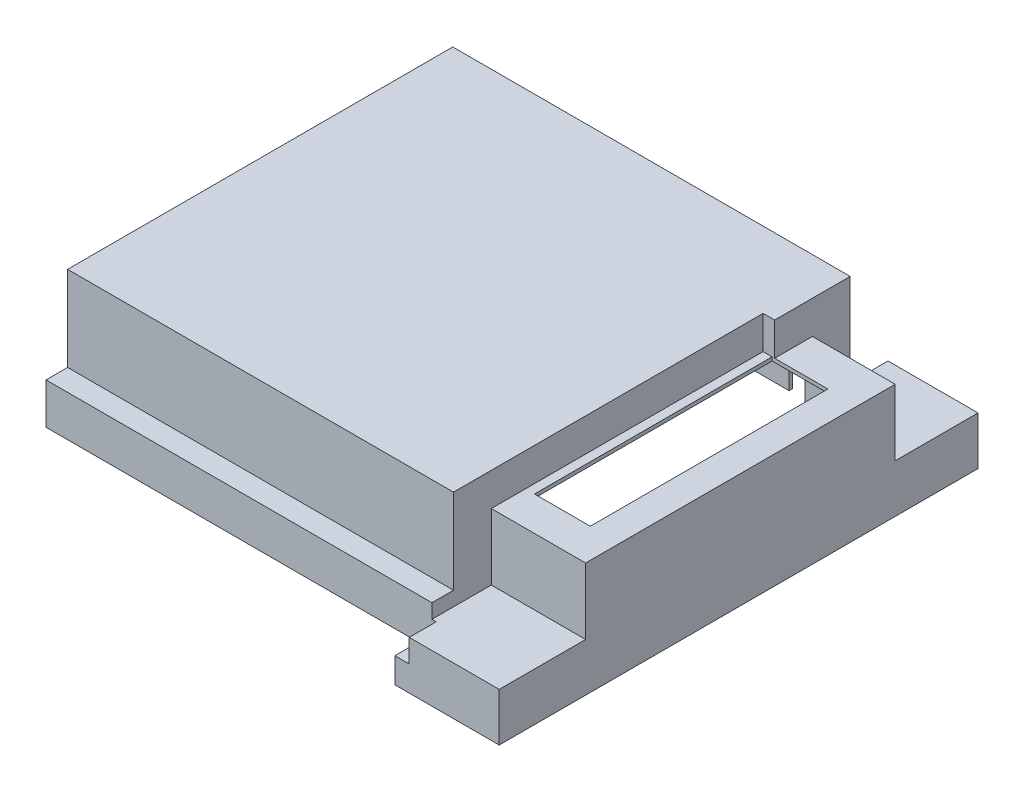
SolidWorks part; units mm, degrees
ref_plane "Front Plane" through (0, 0, 0) normal (0, 0, 1) x (1, 0, 0)
ref_plane "Top Plane" through (0, 0, 0) normal (0, 1, 0) x (1, 0, 0)
ref_plane "Right Plane" through (0, 0, 0) normal (1, 0, 0) x (0, 0, -1)
sketch "Sketch2" plane through (0, 0, 0) normal (0, 1, 0) x (1, 0, 0)
  line L1 (-283.7672, 167.5498) -> (176.6078, 167.5498)
  line L2 (-283.7672, 167.5498) -> (-283.7672, -242.0252)
  line L3 (-283.7672, -242.0252) -> (176.6078, -242.0252)
  line L4 (176.6078, 167.5498) -> (176.6078, -242.0252)
  dimension "D1" = 409.575
  dimension "D2" = 460.375
sketch "Sketch4" plane through (0, 0, 0) normal (0, 1, 0) x (1, 0, 0)
  line L1 (176.6078, -221.3877) -> (-167.5622, -221.3877)
  line L2 (176.6078, 167.5498) -> (176.6078, -242.0252) construction
  line L4 (-167.5622, -221.3877) -> (-167.5622, -219.8002)
  line L5 (-283.7672, -242.0252) -> (176.6078, -242.0252) construction
  line L8 (-167.5622, -219.8002) -> (-167.5622, 131.0373)
  line L11 (-167.5622, 131.0373) -> (176.6078, 131.0373)
  line L16 (-167.5622, -221.3877) -> (176.6078, -221.3877)
  line L17 (-167.5622, -221.3877) -> (-167.5622, 131.0373)
  line L19 (176.6078, -221.3877) -> (176.6078, 131.0373)
  dimension "D1" = 352.425
  dimension "D2" = 20.6375
  dimension "D3" = 350.8375
  dimension "D4" = 344.17
sketch "Sketch6" [suppressed] plane through (0, 0, 0) normal (0, 1, 0) x (1, 0, 0)
  line L1 (-169.4672, -222.1815) -> (176.6078, -222.1815)
  line L2 (-169.4672, -222.1815) -> (-169.4672, 129.926)
  line L3 (-169.4672, 129.926) -> (176.6078, 129.926)
  line L4 (176.6078, -222.1815) -> (176.6078, 129.926)
sketch "Sketch7" [suppressed] plane through (0, 0, 0) normal (0, 1, 0) x (1, 0, 0)
  line L1 (-168.1972, -220.9115) -> (176.6078, -220.9115)
  line L2 (-168.1972, -220.9115) -> (-168.1972, 128.656)
  line L3 (-168.1972, 128.656) -> (176.6078, 128.656)
  line L4 (176.6078, -220.9115) -> (176.6078, 128.656)
extrude "HV Top Panel" add sketch "Sketch4" along normal blind 107.95 contours L1 L19 L11 L8 L4 region at (4.5228, 0, 45.1752)
sketch "Sketch10" plane through (0, 0, 0) normal (0, 1, 0) x (1, 0, 0)
  line L0 (160.7328, 167.5498) -> (246.4578, 167.5498) construction
  line L1 (176.6078, 170.7248) -> (249.6328, 170.7248)
  line L2 (176.6078, 170.7248) -> (176.6078, -245.2002)
  line L3 (176.6078, -245.2002) -> (249.6328, -245.2002)
  line L4 (249.6328, 170.7248) -> (249.6328, -245.2002)
  dimension "D1" = 73.025
  dimension "D2" = 3.175
extrude "Interface with Back Cover" add sketch "Sketch10" along normal blind 78.74
sketch "Sketch11" plane through (0, 107.95, 0) normal (0, 1, 0) x (1, 0, 0)
  line L0 (176.6078, 131.0373) -> (176.6078, -221.3877) construction
  line L1 (249.6328, -245.2002) -> (166.4478, -245.2002)
  line L2 (249.6328, -245.2002) -> (249.6328, -169.0002)
  line L3 (249.6328, -169.0002) -> (166.4478, -169.0002)
  line L4 (166.4478, -245.2002) -> (166.4478, -169.0002)
  line L5 (176.6078, -221.3877) -> (176.6078, 131.0373) construction
  line L6 (249.6328, 170.7248) -> (176.6078, 170.7248)
  line L7 (249.6328, 170.7248) -> (249.6328, 97.6998)
  line L8 (249.6328, 97.6998) -> (176.6078, 97.6998)
  line L9 (176.6078, 170.7248) -> (176.6078, 97.6998)
  line L10 (176.6078, -221.3877) -> (-167.5622, -221.3877) construction
  line L11 (176.6078, -245.2002) -> (249.6328, -245.2002) construction
  line L12 (249.6328, -245.2002) -> (249.6328, 170.7248) construction
  line L13 (166.4478, -221.3877) -> (-167.5622, -221.3877)
  line L14 (166.4478, -221.3877) -> (166.4478, -202.3377)
  line L15 (166.4478, -202.3377) -> (-167.5622, -202.3377)
  line L16 (-167.5622, -221.3877) -> (-167.5622, -202.3377)
  line L17 (-167.5622, -221.3877) -> (-167.5622, 131.0373) construction
  line M22 (-167.5622, -221.3877) -> (176.6078, -221.3877)
  line M23 (176.6078, -221.3877) -> (176.6078, 131.0373)
  line M25 (-167.5622, 131.0373) -> (-167.5622, -221.3877)
  dimension "D1" = 76.2
  dimension "D2" = 73.025
  dimension "D3" = 10.16
  dimension "D4" = 19.05
extrude "Inteface with Motor Disconnect" cut sketch "Sketch11" against normal offset from surface (74.93 mm away) 33.02 contours L4 L15 M25 M22 region at (-0.5572, 107.95, 211.8627) up to face at (108.8215, 0, 37.2377)
extrude "Cut-Extrude6" cut sketch "Sketch11<3>" against normal offset from surface (87.63 mm away) 20.32 contours L4 L1 L2 L3 M23 M22 | L4 L3 M22 M23 | L6 L9 L8 L7 M23 region at (213.1203, 107.95, -134.2123) region at (211.3873, 107.95, 208.1916) region at (171.5278, 107.95, 195.194) up to face at (108.8215, 0, 37.2377)
sketch "Sketch11<3>" plane through (0, 107.95, 0) normal (0, 1, 0) x (1, 0, 0) same geometry as "Sketch11"
sketch "Sketch14" plane through (0, 107.95, 0) normal (0, 1, 0) x (1, 0, 0)
  line L1 (176.6078, -169.0002) -> (166.4478, -169.0002)
  line L2 (176.6078, -169.0002) -> (176.6078, 70.7123)
  line L3 (176.6078, 70.7123) -> (166.4478, 70.7123)
  line L4 (166.4478, -169.0002) -> (166.4478, 70.7123)
  line L7 (-167.5622, 131.0373) -> (176.6078, 131.0373) construction
  dimension "D1" = 60.325
  dimension "D2" = 10.16
extrude "Cut-Extrude3" cut sketch "Sketch14" against normal up to surface (29.21 mm away) up to face at (213.1203, 78.74, 35.6502)
shell "Shell1" thickness 3.175 removed face at (108.8215, 0, 37.2377) outward yes
sketch "Sketch17" plane through (173.4328, 0, 0) normal (-1, 0, 0) x (0, 0, 1)
  line L0 (-134.2123, 23.495) -> (-134.2123, 0) construction
  line L1 (-173.8998, 0) -> (-134.2123, 0)
  line L2 (-173.8998, 0) -> (-173.8998, 3.175)
  line L3 (-173.8998, 3.175) -> (-134.2123, 3.175)
  line L4 (-134.2123, 0) -> (-134.2123, 3.175)
  line L5 (248.3752, 23.495) -> (248.3752, 0) construction
  line L6 (224.5627, 0) -> (248.3752, 0)
  line L7 (224.5627, 0) -> (224.5627, 3.175)
  line L8 (224.5627, 3.175) -> (248.3752, 3.175)
  line L9 (248.3752, 0) -> (248.3752, 3.175)
  dimension "D1" = 3.175
  dimension "D2" = 3.175
extrude "Overlap on Lid" add sketch "Sketch17" along normal blind 12.7
sketch "Sketch15" plane through (0, 0, 0) normal (0, -1, 0) x (1, 0, 0)
  line L0 (249.6328, -170.7248) -> (176.6078, -170.7248) construction
  line L1 (249.6328, 245.2002) -> (249.6328, -170.7248) construction
  line L2 (176.6078, 245.2002) -> (249.6328, 245.2002) construction
  line L3 (249.6328, -170.7248) -> (176.6078, -170.7248)
  line L4 (249.6328, 245.2002) -> (249.6328, -170.7248)
  line L5 (176.6078, 245.2002) -> (249.6328, 245.2002)
  line L6 (176.6078, -170.7248) -> (160.7328, -170.7248)
  line L7 (176.6078, 245.2002) -> (160.7328, 245.2002)
  line L8 (160.7328, 224.5627) -> (-170.7372, 224.5627)
  line L9 (-170.7372, 224.5627) -> (-170.7372, -134.2123)
  line L10 (-170.7372, -134.2123) -> (160.7328, -134.2123)
  line L11 (160.7328, 248.3752) -> (160.7328, 224.5627)
  line L12 (160.7328, -173.8998) -> (252.8078, -173.8998)
  line L13 (252.8078, -173.8998) -> (252.8078, 248.3752)
  line L14 (252.8078, 248.3752) -> (160.7328, 248.3752)
  line L15 (160.7328, 248.3752) -> (160.7328, 224.5627)
  line L16 (160.7328, -173.8998) -> (160.7328, -134.2123) construction
  line L17 (160.7328, -173.8998) -> (160.7328, -170.7248)
  line L18 (160.7328, 224.5627) -> (160.7328, 248.3752) construction
  line L19 (160.7328, -134.2123) -> (160.7328, -173.8998)
  line L20 (160.7328, -173.8998) -> (252.8078, -173.8998)
  line L21 (252.8078, -173.8998) -> (252.8078, 248.3752)
  line L22 (252.8078, 248.3752) -> (160.7328, 248.3752)
  line L23 (160.7328, -134.2123) -> (160.7328, -173.8998)
  line L24 (160.7328, 248.3752) -> (160.7328, 245.2002)
  line M13 (160.7328, -173.8998) -> (252.8078, -173.8998)
  line M14 (252.8078, -173.8998) -> (252.8078, 248.3752)
  line M15 (252.8078, 248.3752) -> (160.7328, 248.3752)
  line M19 (176.6078, 245.2002) -> (249.6328, 245.2002)
  line M20 (249.6328, 245.2002) -> (249.6328, -170.7248)
  line M21 (249.6328, -170.7248) -> (176.6078, -170.7248)
  line M31 (160.7328, 248.3752) -> (160.7328, 224.5627)
  line M32 (160.7328, -134.2123) -> (160.7328, -173.8998)
  dimension "D1" = 0
extrude "Lip" add sketch "Sketch15" along normal blind 19.05 contours L7 L6 M19 M20 M21 M32 M13 M14 M15 M31 region at (250.065, 0, 37.2377)
sketch "Sketch18" plane through (0, 81.915, 0) normal (0, 1, 0) x (1, 0, 0)
  line L0 (166.4478, -169.0002) -> (166.4478, 70.7123) construction
  line L1 (177.5603, -142.0127) -> (226.7728, -142.0127)
  line L2 (177.5603, -142.0127) -> (177.5603, 67.5373)
  line L3 (177.5603, 67.5373) -> (226.7728, 67.5373)
  line L4 (226.7728, -142.0127) -> (226.7728, 67.5373)
  dimension "D1" = 11.1125
  dimension "D2" = 60.325
extrude "Motor Disconnect" cut sketch "Sketch18" against normal blind 7.62
sketch "Sketch19" plane through (0, 0, -134.2123) normal (0, 0, -1) x (-1, 0, 0)
  line L1 (-173.4328, 0) -> (-128.9828, 0)
  line L2 (-173.4328, 0) -> (-173.4328, 105.664)
  line L3 (-173.4328, 105.664) -> (-128.9828, 105.664)
  line L4 (-128.9828, 0) -> (-128.9828, 105.664)
  line L5 (170.7372, 0) -> (-160.7328, 0) construction
  line L6 (-3.8878, 0) -> (167.5622, 0)
  line L7 (-3.8878, 0) -> (-3.8878, 79.375)
  line L8 (-3.8878, 79.375) -> (167.5622, 79.375)
  line L9 (167.5622, 0) -> (167.5622, 79.375)
  line L14 (167.5622, 107.95) -> (167.5622, 0) construction
  line L15 (-176.6078, 107.95) -> (-176.6078, 20.32) construction
  dimension "D2" = 105.664
  dimension "D3" = 79.375
  dimension "D4" = 0
  dimension "D5" = 171.45
  dimension "D6" = 3.175
extrude "LV and HV Panels" cut sketch "Sketch19" against normal blind 7.62
